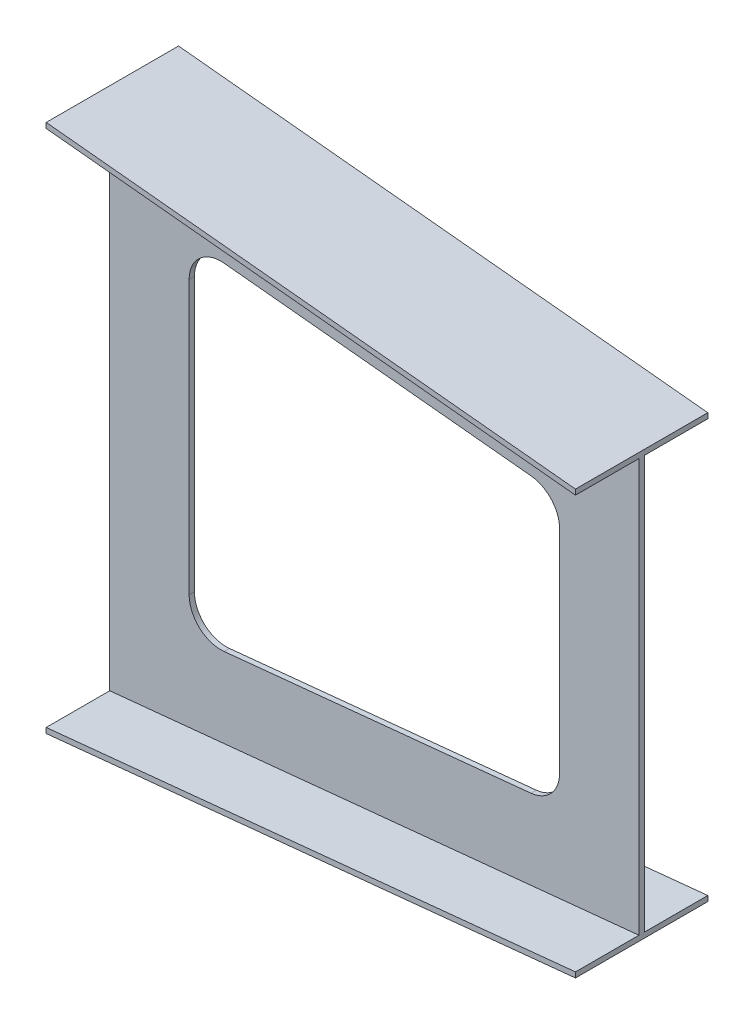
SolidWorks part; units mm, degrees
ref_plane "Front Plane" through (0, 0, 0) normal (0, 0, 1) x (1, 0, 0)
ref_plane "Top Plane" through (0, 0, 0) normal (0, 1, 0) x (1, 0, 0)
ref_plane "Right Plane" through (0, 0, 0) normal (1, 0, 0) x (0, 0, -1)
sketch "Sketch1" plane through (0, 0, 0) normal (1, 0, 0) x (0, 0, -1)
  line L1 (-130, 500) -> (120, 500)
  line L2 (-130, 500) -> (-130, 490)
  line L4 (120, 500) -> (120, 490)
  line L6 (-130, -490) -> (-130, -500)
  line L7 (-130, -500) -> (120, -500)
  line L8 (120, -490) -> (120, -500)
  line L15 (-130, -490) -> (-10, -490)
  line L16 (-5, 490) -> (-5, -490) construction
  line L18 (-130, 490) -> (-10, 490)
  line L19 (0, 0) -> (192.2403, 0) construction
  line L21 (-10, 490) -> (-10, -490)
  line L23 (0, 490) -> (0, -490)
  line L27 (0, 490) -> (120, 490)
  line L28 (0, -490) -> (120, -490)
  dimension "D1" = 250
  dimension "D2" = 10
  dimension "D3" = 1000
  dimension "D4" = 10
ref_plane "Plane2" through (1000, 0, 0) normal (1, 0, 0) x (0, 0, -1)
sketch "Sketch4" plane through (1000, 0, -1000) normal (-1, 0, 0) x (0, 0, 1)
  line L1 (880, 400) -> (1130, 400)
  line L2 (880, 400) -> (880, 390)
  line L4 (1130, 400) -> (1130, 390)
  line L6 (880, -390) -> (880, -400)
  line L7 (880, -400) -> (1130, -400)
  line L8 (1130, -390) -> (1130, -400)
  line L15 (880, -390) -> (1000, -390)
  line L16 (1005, 390) -> (1005, -390) construction
  line L18 (880, 390) -> (1000, 390)
  line L19 (1010, -390) -> (1130, -390)
  line L21 (1000, 390) -> (1000, -390)
  line L23 (1010, 390) -> (1010, -390)
  line L24 (1010, 390) -> (1130, 390)
  line L26 (1010, 490) -> (1010, -490) construction
  line L27 (1000, 0) -> (820.2065, 0) construction
  dimension "D1" = 250
  dimension "D2" = 10
  dimension "D3" = 800
  dimension "D4" = 10
loft "Loft4" add profiles "Sketch1", "Sketch4" connector at (0, 490, 10) connector at (1000, 390, 10)
sketch "Sketch6" plane through (0, 0, 10) normal (0, 0, 1) x (1, 0, 0)
  line L8 (150, -324.2519) -> (850, -254.2519)
  line L9 (850, -254.2519) -> (850, 254.2519)
  line L10 (850, 254.2519) -> (150, 324.2519)
  line L11 (150, 324.2519) -> (150, -324.2519)
  line L12 (215.9702, -317.6548) -> (795.9702, -259.6548)
  line L13 (850, -199.9526) -> (850, 199.9526)
  line L14 (795.9702, 259.6548) -> (215.9702, 317.6548)
  line L15 (150, 257.9526) -> (150, -257.9526)
  arc A0 (150, -257.9526) -> (215.9702, -317.6548) centre (210, -257.9526) ccw
  arc A1 (850, 199.9526) -> (795.9702, 259.6548) centre (790, 199.9526) ccw
  arc A2 (850, -199.9526) -> (795.9702, -259.6548) centre (790, -199.9526) cw
  arc A3 (150, 257.9526) -> (215.9702, 317.6548) centre (210, 257.9526) cw
  dimension "D2" = 60
  dimension "D1" = 150
extrude "Cut-Extrude1" cut sketch "Sketch6" against normal blind 10
